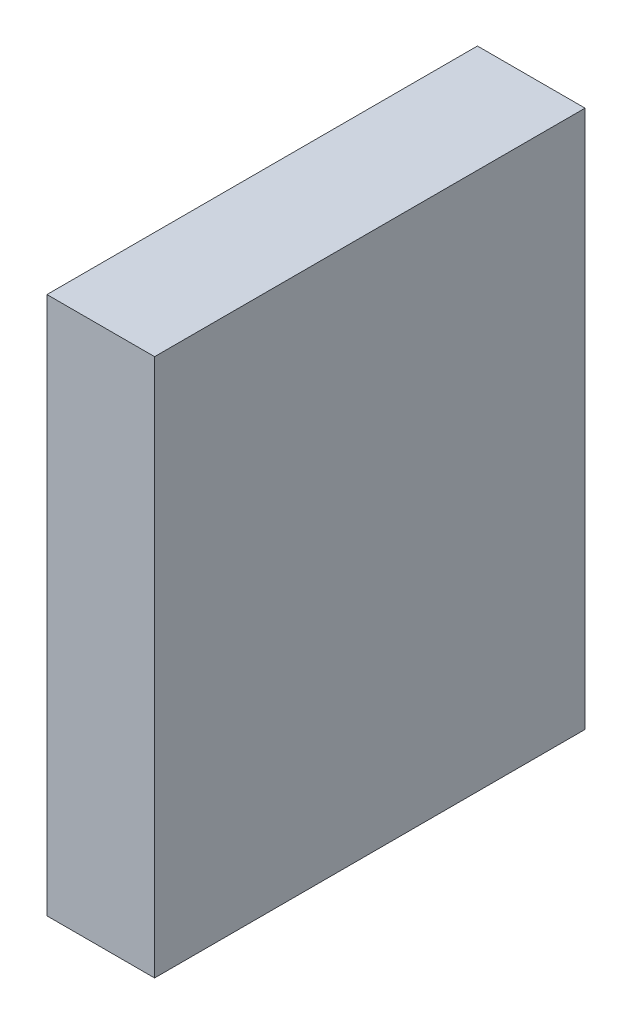
SolidWorks part; units mm, degrees
ref_plane "Front Plane" through (0, 0, 0) normal (0, 0, 1) x (1, 0, 0)
ref_plane "Top Plane" through (0, 0, 0) normal (0, 1, 0) x (1, 0, 0)
ref_plane "Right Plane" through (0, 0, 0) normal (1, 0, 0) x (0, 0, -1)
sketch "Sketch1" plane through (0, 0, 0) normal (1, 0, 0) x (0, 0, -1)
  line L1 (-20, 25) -> (20, 25)
  line L2 (-20, 25) -> (-20, -25)
  line L3 (-20, -25) -> (20, -25)
  line L4 (20, 25) -> (20, -25)
  line L5 (-20, 25) -> (20, -25) construction
  line L6 (-20, -25) -> (20, 25) construction
  point P0 (0, 0)
  dimension "D1" = 50
  dimension "D2" = 40
extrude "Boss-Extrude1" add sketch "Sketch1" along normal blind 10
